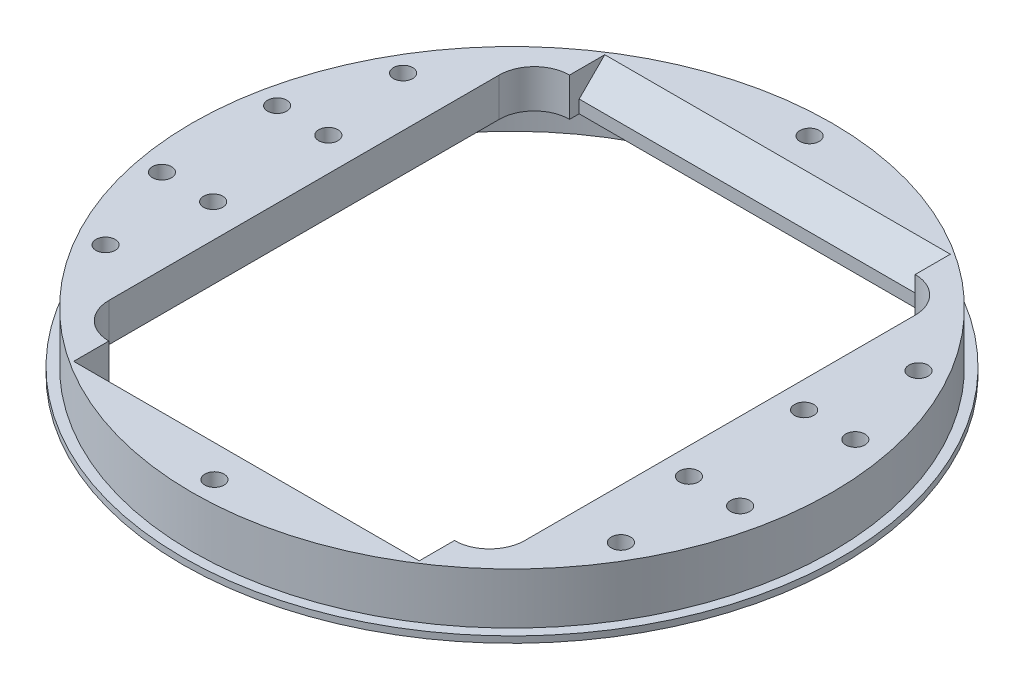
SolidWorks part; units mm, degrees
material "6061 合金"
ref_plane "前视基准面" through (0, 0, 0) normal (0, 0, 1) x (1, 0, 0)
ref_plane "上视基准面" through (0, 0, 0) normal (0, 1, 0) x (1, 0, 0)
ref_plane "右视基准面" through (0, 0, 0) normal (1, 0, 0) x (0, 0, -1)
sketch "草图1" plane through (0, 0, 0) normal (0, 1, 0) x (1, 0, 0)
  circle A0 centre (0, 0) radius 51.5
  circle A1 centre (0, 0) radius 25
  dimension "D1" = 103
  dimension "D2" = 50
extrude "凸台-拉伸1" add sketch "草图1" along normal blind 9
sketch "草图12" plane through (0, 9, 0) normal (0, 1, 0) x (1, 0, 0)
  circle A0 centre (0, 0) radius 51.5
  circle A1 centre (0, 0) radius 50
  dimension "D1" = 100
extrude "切除-拉伸11" cut sketch "草图12" against normal blind 8
sketch "草图3" plane through (0, 9, 0) normal (0, 1, 0) x (1, 0, 0)
  line L1 (-27, -37.5) -> (27, -37.5)
  line L2 (-27, -37.5) -> (-27, 37.5)
  line L3 (-27, 37.5) -> (27, 37.5)
  line L4 (27, -37.5) -> (27, 37.5)
  line L5 (-27, -37.5) -> (27, 37.5) construction
  line L6 (-27, 37.5) -> (27, -37.5) construction
  point P0 (0, 0)
  dimension "D1" = 54
  dimension "D2" = 75
extrude "切除-拉伸2" cut sketch "草图3" against normal through all
chamfer "倒角1" distance 4 angle 45 2 edges at (0, 9, -37.5) (0, 9, 37.5)
sketch "草图4" plane through (0, 0, 0) normal (0, -1, 0) x (1, 0, 0)
  circle A1 centre (0, 0) radius 46.5
  dimension "D1" = 93
extrude "切除-拉伸3" cut sketch "草图4" against normal blind 3
sketch "草图7" plane through (0, 0, 0) normal (0, -1, 0) x (1, 0, 0)
  circle A1 centre (0, 0) radius 46.5 construction
  circle A2 centre (0, 46.5) radius 1.5
  circle A3 centre (40.2702, 23.25) radius 1.5
  circle A4 centre (40.2702, -23.25) radius 1.5
  circle A5 centre (0, -46.5) radius 1.5
  circle A6 centre (-40.2702, -23.25) radius 1.5
  circle A7 centre (-40.2702, 23.25) radius 1.5
  point P17 (0, 0)
  dimension "D1" = 93
  dimension "D2" = 3
  dimension "D3" = 6
extrude "切除-拉伸6" cut sketch "草图7" against normal through all
sketch "草图8" plane through (0, 0, 0) normal (0, -1, 0) x (1, 0, 0)
  circle A0 centre (0, 46.5) radius 3
  circle A1 centre (40.2702, 23.25) radius 3
  circle A2 centre (40.2702, -23.25) radius 3
  circle A3 centre (0, -46.5) radius 3
  circle A4 centre (-40.2702, -23.25) radius 3
  circle A5 centre (-40.2702, 23.25) radius 3
  point P15 (0, 0)
  dimension "D1" = 6
  dimension "D2" = 6
extrude "切除-拉伸7" cut sketch "草图8" against normal blind 3
sketch "草图11" plane through (0, 9, 0) normal (0, 1, 0) x (1, 0, 0)
  line L1 (-32.5, -36) -> (32.5, -36)
  line L2 (-32.5, -36) -> (-32.5, 36)
  line L3 (-32.5, 36) -> (32.5, 36)
  line L4 (32.5, -36) -> (32.5, 36)
  line L5 (-32.5, -36) -> (32.5, 36) construction
  line L6 (-32.5, 36) -> (32.5, -36) construction
  point P0 (0, 0)
  dimension "D1" = 65
  dimension "D2" = 72
extrude "切除-拉伸10" cut sketch "草图11" against normal through all
fillet "圆角1" radius 5.5 4 edges at (-32.5, 4.5, 36) (32.5, 4.5, 36) (32.5, 4.5, -36) (-32.5, 4.5, -36)
extrude "切除-拉伸12" cut sketch "草图13" against normal blind 20
sketch "草图13" plane through (90.5739, 17, 197.9567) normal (0, 1, 0) x (0.9919, 0, 0.1274)
  circle A8 centre (-161.5296, 187.9091) radius 1.5
  circle A9 centre (-153.5947, 188.9283) radius 1.5
  circle A10 centre (-159.2364, 170.0558) radius 1.5
  circle A11 centre (-151.3016, 171.075) radius 1.5
  circle A12 centre (-79.8506, 198.4004) radius 1.5
  circle A13 centre (-71.9158, 199.4196) radius 1.5
  circle A14 centre (-77.5574, 180.5471) radius 1.5
  circle A15 centre (-69.6226, 181.5663) radius 1.5
sketch "草图14" plane through (0, 0, 0) normal (0, -1, 0) x (1, 0, 0)
  line L0 (-51.5, 0) -> (51.5, 0) construction
  circle A0 centre (-45.7, 9) radius 3
  circle A1 centre (0, 0) radius 51.5 construction
  circle A2 centre (44.65, 9) radius 3
  circle A3 centre (-45.7, -9) radius 3
  circle A4 centre (44.65, -9) radius 3
  dimension "D1" = 6
  dimension "D2" = 6
extrude "切除-拉伸13" cut sketch "草图14" against normal blind 3
